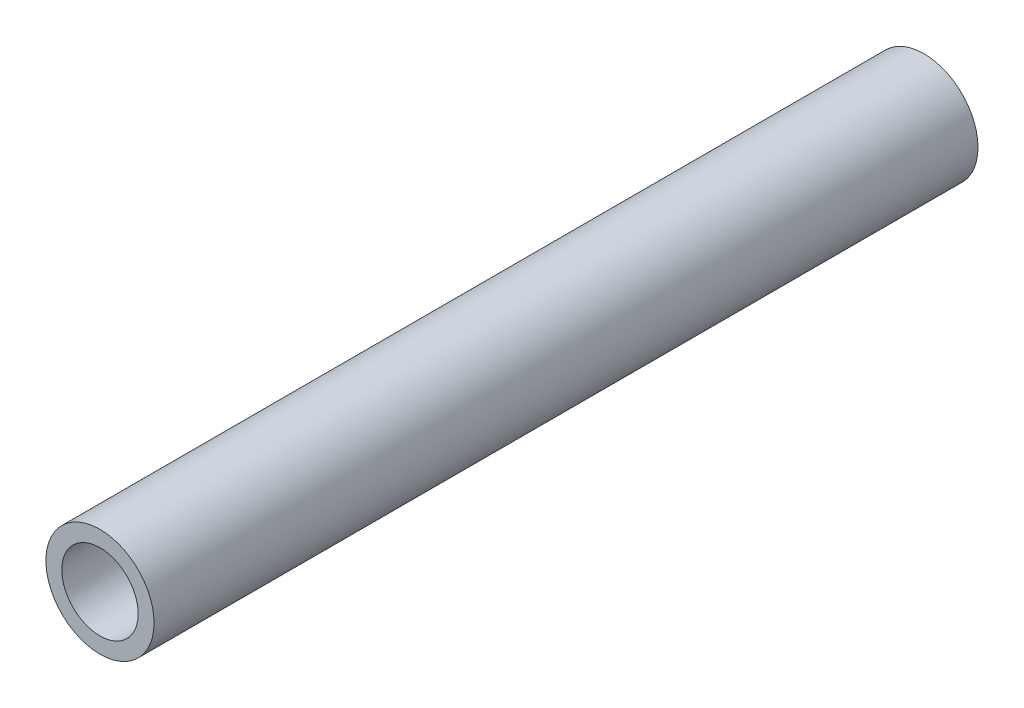
SolidWorks part; units mm, degrees
ref_plane "Front Plane" through (0, 0, 0) normal (0, 0, 1) x (1, 0, 0)
ref_plane "Top Plane" through (0, 0, 0) normal (0, 1, 0) x (1, 0, 0)
ref_plane "Right Plane" through (0, 0, 0) normal (1, 0, 0) x (0, 0, -1)
sketch "Sketch1" plane through (0, 0, 0) normal (0, 0, 1) x (1, 0, 0)
  circle A0 centre (0, 0) radius 13.335
  dimension "Pipe OD" = 26.67
extrude "Extrude-Thin1" add sketch "Sketch1" along normal mid plane 203.2 thin thin type one direction reverse wall 3.9116
